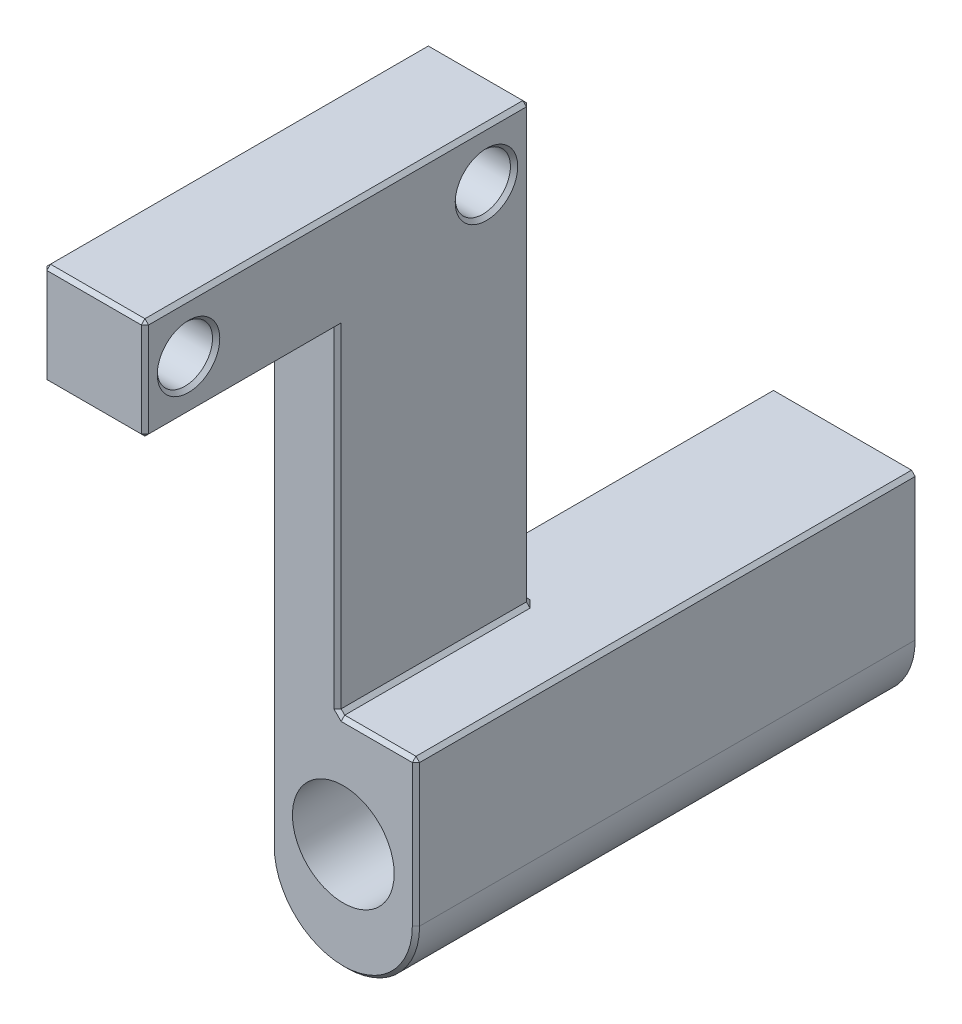
SolidWorks part; units mm, degrees
ref_plane "Front Plane" through (0, 0, 0) normal (0, 0, 1) x (1, 0, 0)
ref_plane "Top Plane" through (0, 0, 0) normal (0, 1, 0) x (1, 0, 0)
ref_plane "Right Plane" through (0, 0, 0) normal (1, 0, 0) x (0, 0, -1)
sketch "Sketch1" plane through (0, 0, 0) normal (0, 0, 1) x (1, 0, 0)
  line L0 (0, 30.5105) -> (0, -32.2426) construction
  line L1 (-36.6434, 0) -> (44.8163, 0) construction
  line L2 (0, 35) -> (0, 28)
  line L3 (0, 28) -> (2.4, 28)
  line L4 (2.4, 28) -> (2.4, -10)
  line L5 (2.4, -10) -> (7, -10)
  line L6 (7, -10) -> (7, 35)
  line L7 (7, 35) -> (0, 35)
  point P11 (0, 0)
  point P12 (0, 30.5105)
  point P13 (4.7, -10)
  dimension "D1" = 7
  dimension "D2" = 7
  dimension "D3" = 2.4
  dimension "D4" = 35
  dimension "D5" = 10
extrude "Boss-Extrude1" add sketch "Sketch1" along normal blind 26.5
sketch "Sketch2" plane through (0, 0, 0) normal (0, 0, 1) x (1, 0, 0)
  line L0 (-15.7211, 0) -> (17.8263, 0) construction
  line L1 (0, 43.2729) -> (0, -17.0695) construction
  line L2 (2.4, 28) -> (2.4, -10) construction
  line L3 (2.4, 5) -> (12.4, 5)
  line L4 (2.4, 5) -> (2.4, -10)
  line L5 (2.4, -10) -> (12.4, -10)
  line L6 (12.4, 5) -> (12.4, -10)
  dimension "D1" = 15
  dimension "D2" = 10
  dimension "D3" = 10
extrude "Boss-Extrude2" add sketch "Sketch2" against normal blind 21.1 and the other way up to surface other way up to face at (3.1333, 17.6667, 26.5)
sketch "Sketch3" plane through (0, 0, 0) normal (1, 0, 0) x (0, 0, -1)
  line L0 (0, 48.2929) -> (0, -22.7771) construction
  line L1 (-26.5, -10) -> (21.1, -10) construction
  line L2 (-13.25, -10) -> (-26.5, -10)
  line L3 (-13.25, -10) -> (-13.25, 28)
  line L4 (-13.25, 28) -> (-26.5, 28)
  line L5 (-26.5, -10) -> (-26.5, 28)
  line L6 (-26.5, 5) -> (-26.5, 35) construction
  dimension "D1" = 13.25
  dimension "D2" = 38
extrude "Cut-Extrude1" cut sketch "Sketch3" along normal blind 21.1
sketch "Sketch4" plane through (0, 0, 0) normal (0, 0, 1) x (1, 0, 0)
  line L0 (-17.1399, 0) -> (25.3614, 0) construction
  line L1 (12.4, -10) -> (12.4, 5) construction
  circle A0 centre (7.4, -2.5) radius 1.8
  dimension "D1" = 3.6
  dimension "D2" = 5
  dimension "D3" = 2.5
extrude "Cut-Extrude2" cut sketch "Sketch4" against normal through all both and the other way through all
sketch "Sketch5" plane through (0, 0, 13.25) normal (0, 0, 1) x (1, 0, 0)
  circle A0 centre (7.4, -2.5) radius 3.5
  dimension "D1" = 7
extrude "Cut-Extrude3" cut sketch "Sketch5" against normal blind 11.1
sketch "Sketch6" plane through (0, 0, 0) normal (1, 0, 0) x (0, 0, -1)
  line L0 (0, 42.402) -> (0, -12.1008) construction
  line L1 (-42.7056, 31.5) -> (21.9587, 31.5) construction
  line L2 (-26.5, 35) -> (0, 35) construction
  line L3 (-13.25, 42.402) -> (-13.25, -12.8824) construction
  circle A0 centre (-3, 31.5) radius 1.9
  circle A1 centre (-23.5, 31.5) radius 1.9
  dimension "D3" = 3.8
  dimension "D4" = 10.25
  dimension "D1" = 3.5
  dimension "D2" = 13.25
extrude "Cut-Extrude4" cut sketch "Sketch6" along normal through all
fillet "Fillet1" radius 5 2 edges at (2.4, -10, -3.925) (12.4, -10, -3.925)
chamfer "Chamfer1" distance 0.25 angle 45 27 edges at (7, 29.6, 23.5) (7, 29.6, 3) (0, 31.5, 25.4) (0, 31.5, 1.1) (2.4, 5, -10.55) (9.7, 5, 13.25) (4.7, 5, 0) (7, 28, 19.875) (7, 31.5, 26.5) (7, 35, 13.25) (7, 16.5, 13.25) (7, 5, 6.625) (7, 20, 0) (0, 35, 13.25) (3.5, 35, 26.5) (0, 31.5, 26.5) (3.5, 35, 0) (0, 31.5, 0) (2.4, 16.5, 0) (1.2, 28, 0) (0, 28, 13.25) (3.5, 28, 26.5) (3.8645, -8.5355, 13.25) (2.4, 11.5, 13.25) (12.4, 5, -3.925) (12.4, 0, 13.25) (10.9355, -8.5355, 13.25)
